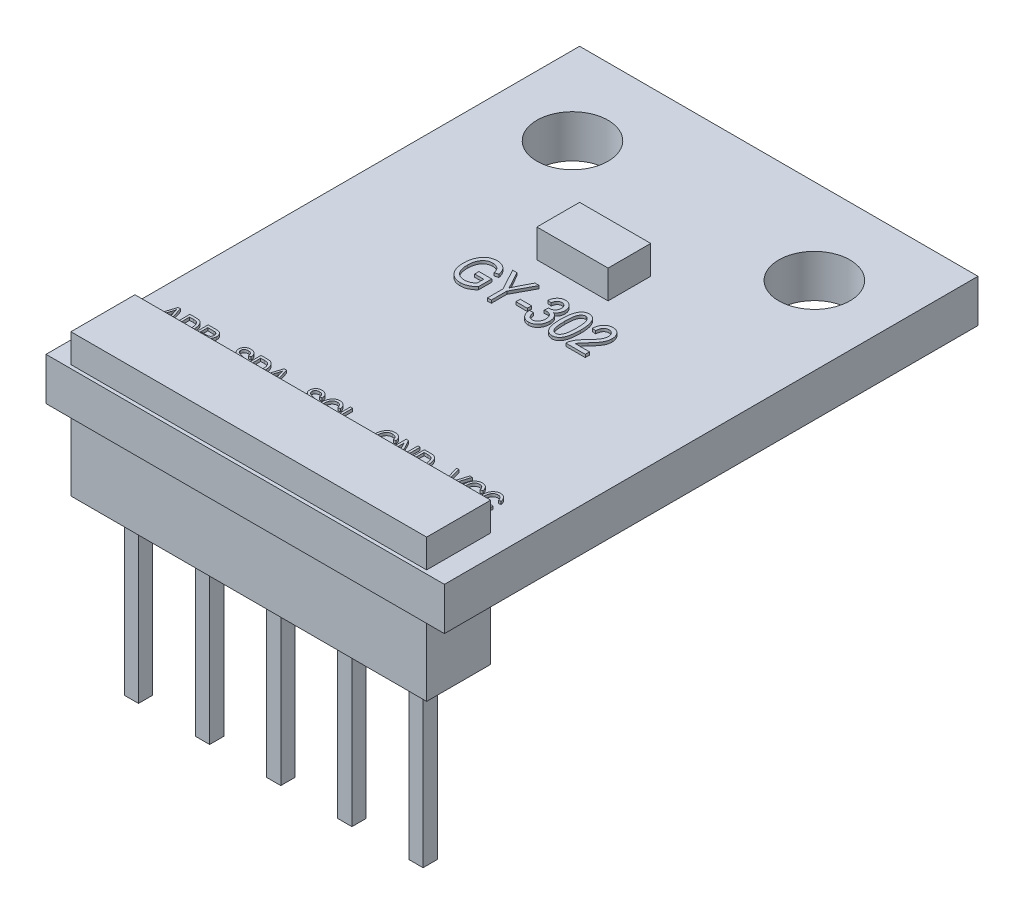
SolidWorks part; units mm, degrees
ref_plane "Front Plane" through (0, 0, 0) normal (0, 0, 1) x (1, 0, 0)
ref_plane "Top Plane" through (0, 0, 0) normal (0, 1, 0) x (1, 0, 0)
ref_plane "Right Plane" through (0, 0, 0) normal (1, 0, 0) x (0, 0, -1)
sketch "Sketch1" plane through (0, 0, 0) normal (0, 1, 0) x (1, 0, 0)
  line L0 (0, 17.5) -> (0, -1.25) construction
  line L1 (-7, 17.5) -> (7, 17.5)
  line L2 (-7, 17.5) -> (-7, -1.25)
  line L3 (-7, -1.25) -> (7, -1.25)
  line L4 (7, 17.5) -> (7, -1.25)
  line L5 (-7, 0) -> (7, 0) construction
  line L6 (1.25, 11) -> (-1.25, 11) construction
  line L7 (3.75, 1.125) -> (3.75, -1.125) construction
  line L8 (-6.25, 1.125) -> (6.25, 1.125)
  line L9 (-6.25, 1.125) -> (-6.25, -1.125)
  line L10 (-6.25, -1.125) -> (6.25, -1.125)
  line L11 (1.25, 11.75) -> (-1.25, 11.75)
  line L12 (1.25, 11.75) -> (1.25, 10.25)
  line L13 (1.25, 10.25) -> (-1.25, 10.25)
  line L14 (-1.25, 11.75) -> (-1.25, 10.25)
  line L15 (6.25, 1.125) -> (6.25, -1.125)
  line L16 (5, 1.125) -> (5, -1.125) construction
  line L17 (-6.25, 1.625) -> (6.25, 1.625) construction
  line L18 (4.75, 0.25) -> (5.25, 0.25)
  line L19 (4.75, 0.25) -> (4.75, -0.25)
  line L20 (4.75, -0.25) -> (5.25, -0.25)
  line L21 (5.25, 0.25) -> (5.25, -0.25)
  line L22 (3.75, 1.625) -> (1.25, 1.625) construction
  circle A0 centre (-4.25, 14.5) radius 1.25
  circle A1 centre (4.25, 14.5) radius 1.25
  point P22 (0, 0)
  point P33 (5, 0)
  point P36 (3.75, 1.625)
  point P37 (1.25, 1.625)
  point P39 (-1.25, 1.625)
  point P40 (-3.75, 1.625)
  point P41 (-6.25, 1.625)
  dimension "D1" = 14
  dimension "D3" = 8.5
  dimension "D4" = 2.5
  dimension "D2" = 18.75
  dimension "D5" = 3
  dimension "D6" = 1.5
  dimension "D7" = 2.5
  dimension "D8" = 6.5
  dimension "D9" = 2.25
  dimension "D10" = 1.25
  dimension "D11" = 12.5
  dimension "D12" = 2.5
  dimension "D13" = 0.5
  dimension "D14" = 0.5
  dimension "D16" = 2.5
  dimension "D15" = 5
extrude "Boss-Extrude1" add sketch "Sketch1" along normal blind 1.5 contours L4 L1 L2 L3 L8 L15 L10 L9 L14 L11 L12 L13 A0 A1 region at (0, 0, -8.8276)
extrude "Boss-Extrude2" add sketch "Sketch1<3>" along normal blind 2.5 contours L11 L14 L13 L12 region at (0, 0, -11)
sketch "Sketch1<3>" plane through (0, 0, 0) normal (0, 1, 0) x (1, 0, 0) same geometry as "Sketch1"
extrude "Boss-Extrude3" add sketch "Sketch1<4>" along normal blind 1 and the other way up to surface from vertex contours L15 L8 L9 L10 L18 L21 L20 L19 | L21 L18 L19 L20 region at (-0.0448, 0, 0) region at (5, 0, 0) other way up to face at (0, 0, 0) starting at point (7, 1.5, 1.25)
sketch "Sketch1<4>" plane through (0, 0, 0) normal (0, 1, 0) x (1, 0, 0) same geometry as "Sketch1"
extrude "Boss-Extrude4" add sketch "Sketch1<6>" against normal blind 2.5 contours L15 L8 L9 L10 L18 L21 L20 L19 | L21 L18 L19 L20 region at (-0.0448, 0, 0) region at (5, 0, 0)
sketch "Sketch1<6>" plane through (0, 0, 0) normal (0, 1, 0) x (1, 0, 0) same geometry as "Sketch1"
extrude "Boss-Extrude5" add sketch "Sketch1<7>" against normal blind 8.5 contours L21 L18 L19 L20 region at (5, 0, 0)
sketch "Sketch1<7>" plane through (0, 0, 0) normal (0, 1, 0) x (1, 0, 0) same geometry as "Sketch1"
pattern_linear "LPattern1" count 5 spacing 2.5 along (-1, 0, 0) of "Boss-Extrude5"
sketch "Sketch2" plane through (0, 0, 0) normal (0, 1, 0) x (1, 0, 0)
  line L0 (-7, 8.125) -> (7, 8.125) construction
  line L1 (-7, 17.5) -> (-7, -1.25) construction
  line L2 (7, 17.5) -> (7, -1.25) construction
  text T0 "VCC" font "Arial Narrow" height in points 3
  text T1 "GND" font "Arial Narrow" height in points 3
  text T2 "SCL" font "Arial Narrow" height in points 3
  text T3 "SDA" font "Arial Narrow" height in points 3
  text T4 "ADR" font "Arial Narrow" height in points 3
  text T5 "GY-302" font "Arial Narrow" height in points 5
  point P0 (3.75, 1.625)
  point P2 (1.25, 1.625)
  point P4 (-1.25, 1.625)
  point P6 (-3.75, 1.625)
  point P8 (-6.25, 1.625)
extrude "Boss-Extrude6" add sketch "Sketch2" along normal blind 0.1 from vertex starting at point (7, 1.5, 1.25)
equation "\"D11@Sketch1\"=\"D12@Sketch1\" * 5"
